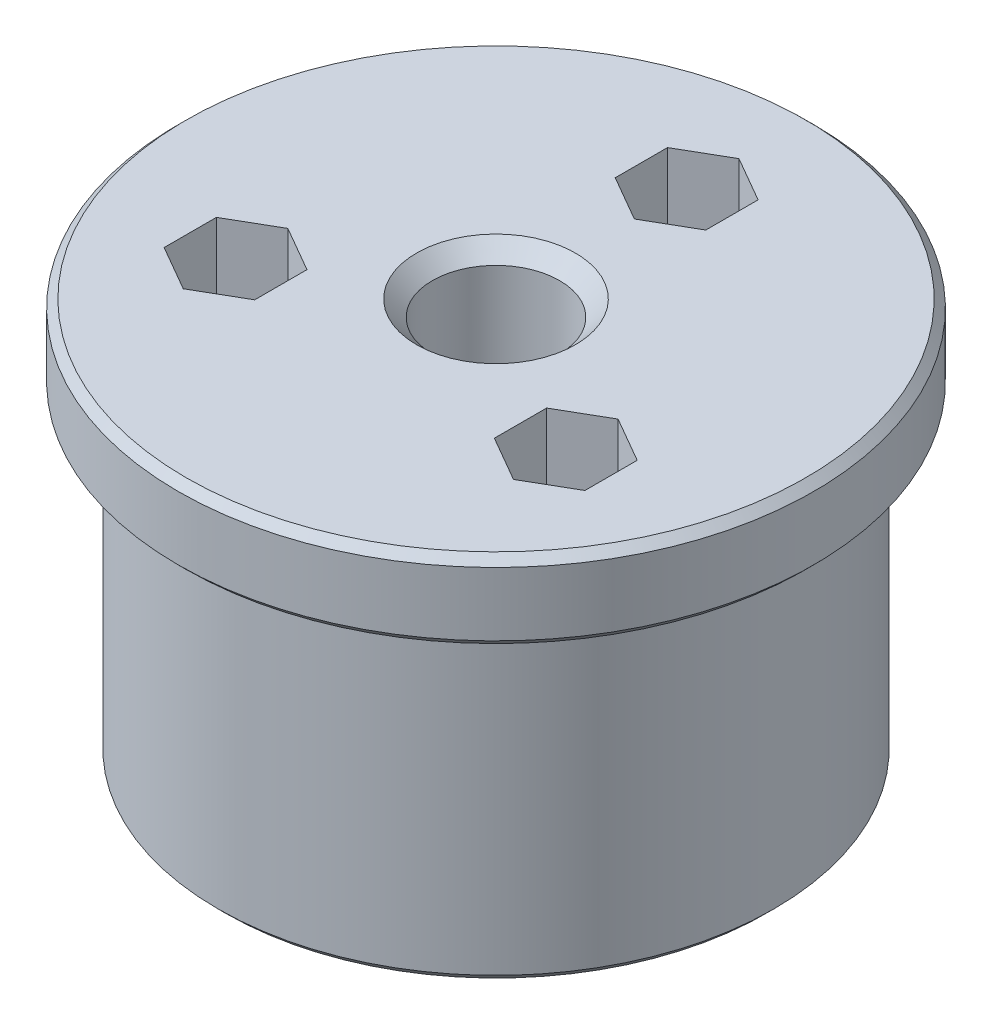
SolidWorks part; units mm, degrees
ref_plane "Front" through (0, 0, 0) normal (0, 0, 1) x (1, 0, 0)
ref_plane "Top" through (0, 0, 0) normal (0, 1, 0) x (1, 0, 0)
ref_plane "Right" through (0, 0, 0) normal (1, 0, 0) x (0, 0, -1)
sketch "Эскиз1" plane through (0, 0, 0) normal (0, 1, 0) x (1, 0, 0)
  circle A0 centre (0, 0) radius 20
  dimension "D1" = 40
extrude "Бобышка-Вытянуть1" add sketch "Эскиз1" along normal blind 25
sketch "Эскиз2" plane through (0, 0, 0) normal (0, 1, 0) x (1, 0, 0)
  circle A0 centre (0, 0) radius 17.5
  dimension "D1" = 35
extrude "Вырез-Вытянуть1" cut sketch "Эскиз2" along normal blind 20 flip side to cut
sketch "Эскиз3" plane through (0, 0, 0) normal (0, -1, 0) x (1, 0, 0)
  circle A0 centre (0, 0) radius 15.1
  dimension "D1" = 30.2
extrude "Вырез-Вытянуть2" cut sketch "Эскиз3" against normal blind 6
sketch "Эскиз4" plane through (0, 0, 0) normal (0, 1, 0) x (1, 0, 0)
  line L1 (0, 15.2909) -> (-2.85, 13.6454)
  line L2 (-2.85, 13.6454) -> (-2.85, 10.3546)
  line L3 (-2.85, 10.3546) -> (0, 8.7091)
  line L4 (0, 8.7091) -> (2.85, 10.3546)
  line L5 (2.85, 10.3546) -> (2.85, 13.6454)
  line L6 (2.85, 13.6454) -> (0, 15.2909)
  circle A0 centre (0, 0) radius 4
  circle A1 centre (0, 0) radius 12 construction
  circle A2 centre (0, 12) radius 1.6
  circle A3 centre (0, 12) radius 2.85 construction
  dimension "D1" = 24
  dimension "D2" = 8
  dimension "D3" = 3.2
  dimension "D4" = 5.7
extrude "Вырез-Вытянуть3" cut sketch "Эскиз4" along normal through all contours A0 region at (0, 0, 0)
extrude "Вырез-Вытянуть4" cut sketch "Эскиз4<3>" along normal through all contours A2 region at (0, 0, -12)
sketch "Эскиз4<3>" plane through (0, 0, 0) normal (0, 1, 0) x (1, 0, 0) same geometry as "Эскиз4"
extrude "Вырез-Вытянуть5" cut sketch "Эскиз4<4>" along normal through all from offset 15 contours L5 L6 L1 L2 L3 L4 A2 region at (1.3815, 0, -14.3928)
sketch "Эскиз4<4>" plane through (0, 0, 0) normal (0, 1, 0) x (1, 0, 0) same geometry as "Эскиз4"
pattern_circular "Круговой массив1" count 3 over 360 about axis through (0, 20, 0) along (0, -1, 0) of "Вырез-Вытянуть5", "Вырез-Вытянуть4" reverse direction yes
chamfer "Фаска1" distance 0.5 angle 45 3 edges at (0, 25, 20) (0, 20, 20) (0, 0, 17.5)
chamfer "Фаска2" distance 1 angle 45 2 edges at (0, 25, 4) (0, 6, -4)
fillet "Скругление1" radius 0.6 1 edges at (0, 6, -15.1)
